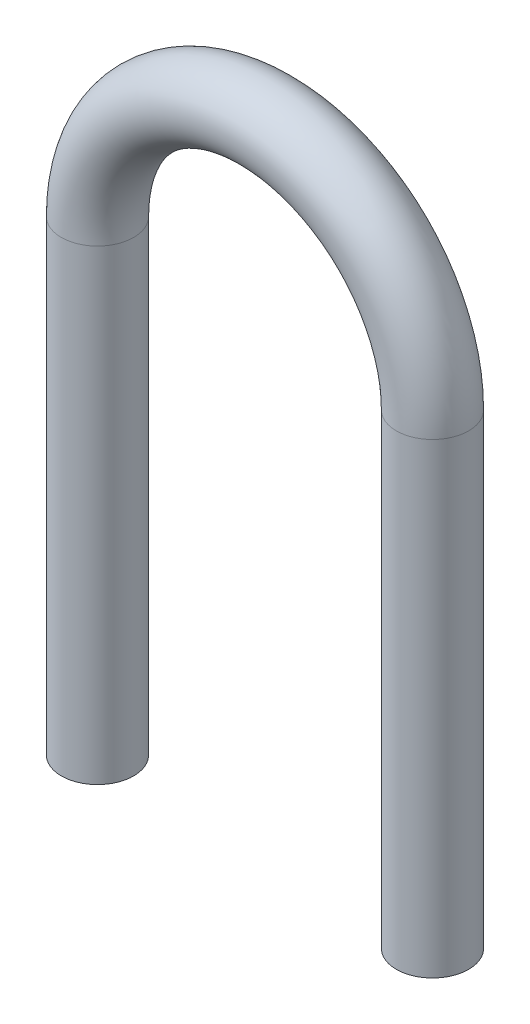
SolidWorks part; units mm, degrees
material "Stainless Steel (ferritic)"
ref_plane "Front Plane" through (0, 0, 0) normal (0, 0, 1) x (1, 0, 0)
ref_plane "Top Plane" through (0, 0, 0) normal (0, 1, 0) x (1, 0, 0)
ref_plane "Right Plane" through (0, 0, 0) normal (1, 0, 0) x (0, 0, -1)
sketch "Sketch1" plane through (0, 0, 0) normal (0, 0, 1) x (1, 0, 0)
  line L0 (-13.9, -13.9) -> (-13.9, -52.6)
  line L1 (13.9, -13.9) -> (13.9, -52.6)
  line L2 (-11.35, -52.6) -> (-11.35, -13.9) construction
  line L3 (-11.35, -13.9) -> (11.35, -13.9) construction
  line L4 (11.35, -13.9) -> (11.35, -52.6) construction
  line L5 (-16.45, -13.9) -> (-16.45, -52.6) construction
  line L6 (-16.45, -52.6) -> (16.45, -52.6) construction
  line L7 (16.45, -52.6) -> (16.45, -13.9) construction
  line L8 (-16.45, -33.25) -> (-11.35, -33.25) construction
  line L9 (16.45, -33.25) -> (11.35, -33.25) construction
  arc A0 (13.9, -13.9) -> (-13.9, -13.9) centre (0, -13.9) ccw
  point P3 (0, 0)
  point P9 (0, -13.9)
  point P16 (0, -52.6)
  point P19 (-11.35, -33.25)
  point P22 (0, 0)
  point P23 (0, 0)
  point P24 (0, 0)
  point P25 (-13.9, -33.25)
  point P26 (14.3, -47.5825)
  dimension "D1" = 22.7
  dimension "D2" = 32.9
  dimension "D3" = 52.6
ref_plane "Plane1" through (0, -52.6, 0) normal (0, 1, 0) x (1, 0, 0)
sketch "Sketch2" plane through (0, -52.6, 0) normal (0, 1, 0) x (1, 0, 0)
  circle A0 centre (-13.9, 0) radius 3
  dimension "D1" = 6
sweep "Sweep1" add profiles "Sketch2" path "Sketch1"
